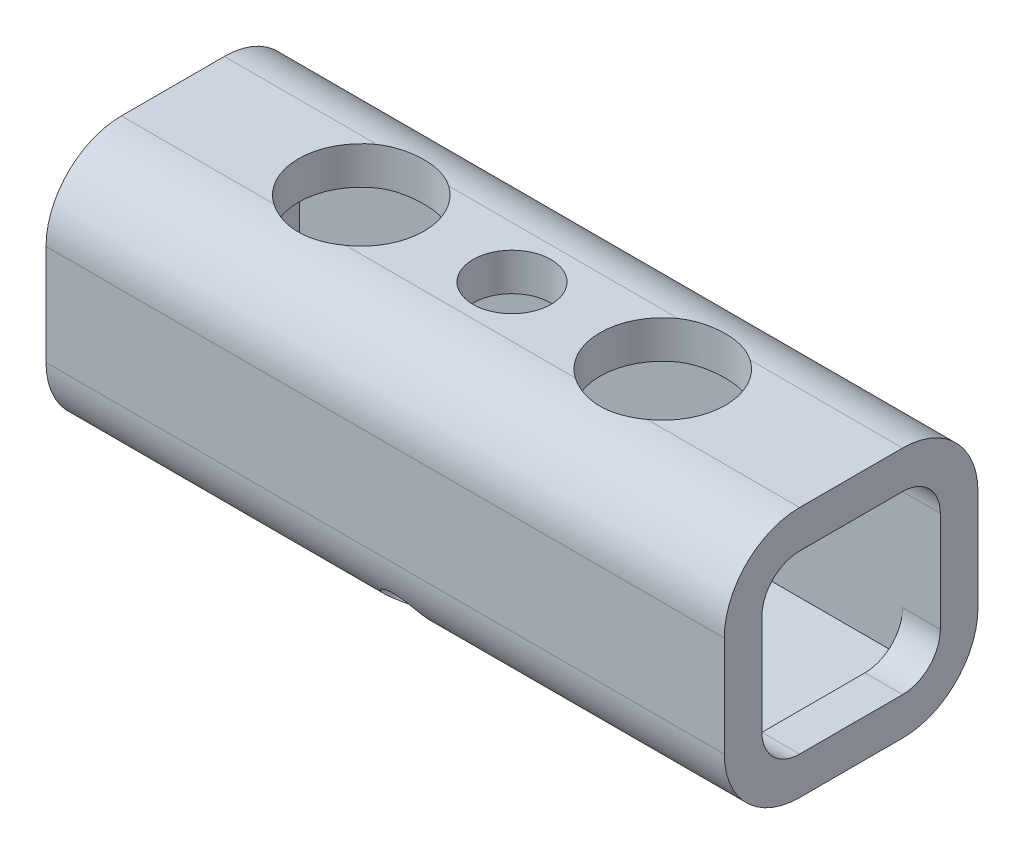
SolidWorks part; units mm, degrees
ref_plane "Front Plane" through (0, 0, 0) normal (0, 0, 1) x (1, 0, 0)
ref_plane "Top Plane" through (0, 0, 0) normal (0, 1, 0) x (1, 0, 0)
ref_plane "Right Plane" through (0, 0, 0) normal (1, 0, 0) x (0, 0, -1)
sketch "Sketch1" plane through (0, 0, 0) normal (0, 1, 0) x (1, 0, 0)
  line L0 (-12, 0) -> (12, 0) construction
  line L1 (-12, 3.55) -> (12, 3.55)
  line L2 (-12, 3.55) -> (-12, -3.55)
  line L3 (-12, -3.55) -> (12, -3.55)
  line L4 (12, 3.55) -> (12, -3.55)
  line L5 (-12, 3.55) -> (12, -3.55) construction
  line L6 (-12, -3.55) -> (12, 3.55) construction
  line L7 (0, 3.55) -> (0, -3.55) construction
  line L8 (-13.5, 5.05) -> (-13.5, -5.05)
  line L9 (-13.5, -5.05) -> (13.5, -5.05)
  line L10 (13.5, 5.05) -> (13.5, -5.05)
  line L11 (-13.5, 5.05) -> (13.5, 5.05)
  circle A0 centre (6, 0) radius 2.5
  circle A1 centre (0, 0) radius 1.55
  circle A2 centre (-6, 0) radius 2.5
  point P0 (0, 0)
  dimension "D3" = 3.1
  dimension "D4" = 5
  dimension "D1" = 7.1
  dimension "D2" = 24
  dimension "D5" = 12
  dimension "D6" = 1.5
extrude "Boss-Extrude2" add sketch "Sketch1" along normal blind 10 contours A2 | L4 L1 L2 L3 A0 A1 A2 | L11 L8 L9 L10 L1 L4 L3 L2 | A1 | A0 region at (0, 0, -3.2997) region at (0, 0, -4.7617) region at (6, 0, 0) region at (0, 0, 0) region at (-6, 0, 0)
extrude "Cut-Extrude2" cut sketch "Sketch1<5>" against normal blind 2.7 from surface contours A2 | A1 | A0 starting at face at (0, 10, 0)
sketch "Sketch1<5>" plane through (0, 0, 0) normal (0, 1, 0) x (1, 0, 0) same geometry as "Sketch1"
fillet "Fillet1" radius 3 4 edges at (0, 0, -5.05) (0, 0, 5.05) (0, 10, -5.05) (0, 10, 5.05)
extrude "Cut-Extrude3" cut sketch "Sketch1<6>" along normal blind 6.5 from offset 1.3 contours L4 L1 L2 L3 A0 A1 A2 region at (0, 0, -3.2997)
sketch "Sketch1<6>" plane through (0, 0, 0) normal (0, 1, 0) x (1, 0, 0) same geometry as "Sketch1"
sketch "Sketch2" plane through (13.5, 0, 0) normal (1, 0, 0) x (0, 0, -1)
  line L4 (-5.05, 5) -> (5.05, 5) construction
  line L5 (-5.05, 7) -> (-5.05, 3) construction
  line L6 (5.05, 7) -> (5.05, 3) construction
  line L7 (0, 10) -> (0, 0) construction
  line L8 (-3.55, 7) -> (-3.55, 3)
  line L9 (-2.05, 1.5) -> (2.05, 1.5)
  line L10 (3.55, 3) -> (3.55, 7)
  line L11 (2.05, 8.5) -> (-2.05, 8.5)
  line L12 (-3.55, 7) -> (-3.55, 3)
  line L13 (-2.05, 1.5) -> (2.05, 1.5)
  line L14 (3.55, 3) -> (3.55, 7)
  line L15 (2.05, 8.5) -> (-2.05, 8.5)
  line L16 (2.05, 10) -> (-2.05, 10) construction
  circle A4 centre (0, 5) radius 1.475
  arc A8 (-3.55, 3) -> (-2.05, 1.5) centre (-2.05, 3) ccw
  arc A9 (2.05, 1.5) -> (3.55, 3) centre (2.05, 3) ccw
  arc A10 (3.55, 7) -> (2.05, 8.5) centre (2.05, 7) ccw
  arc A11 (-2.05, 8.5) -> (-3.55, 7) centre (-2.05, 7) ccw
  arc A12 (-3.55, 3) -> (-2.05, 1.5) centre (-2.05, 3) ccw
  arc A13 (2.05, 1.5) -> (3.55, 3) centre (2.05, 3) ccw
  arc A14 (3.55, 7) -> (2.05, 8.5) centre (2.05, 7) ccw
  arc A15 (-2.05, 8.5) -> (-3.55, 7) centre (-2.05, 7) ccw
  dimension "D2" = 2.95
  dimension "D1" = 1.5
extrude "Cut-Extrude4" cut sketch "Sketch2" against normal offset from surface (25 mm away) 2 contours L15 A15 L12 A12 L13 A13 L14 A14 A4 | A4 region at (13.5, 7.9902, 3.0402) region at (13.5, 5, 0) up to face at (-13.5, 5, 0)
extrude "Cut-Extrude5" cut sketch "Sketch2<3>" against normal through all both and the other way through all contours A4 region at (13.5, 5, 0)
sketch "Sketch2<3>" plane through (13.5, 0, 0) normal (1, 0, 0) x (0, 0, -1) same geometry as "Sketch2"
ref_plane "Plane1" through (0, 0, 0) normal (0, -0.7071, 0.7071) x (1, 0, 0)
sketch "Sketch3" plane through (0, 0, 0) normal (0, -0.7071, 0.7071) x (1, 0, 0)
  line L0 (-13.5, 3.5709) -> (13.5, 3.5709) construction
  line L1 (-13.5, 5.6922) -> (-13.5, 1.4496) construction
  line L2 (13.5, 1.4496) -> (13.5, 5.6922) construction
  circle A0 centre (0, 3.5709) radius 0.9
  dimension "D1" = 1.8
extrude "Cut-Extrude6" cut sketch "Sketch3" along normal through all
